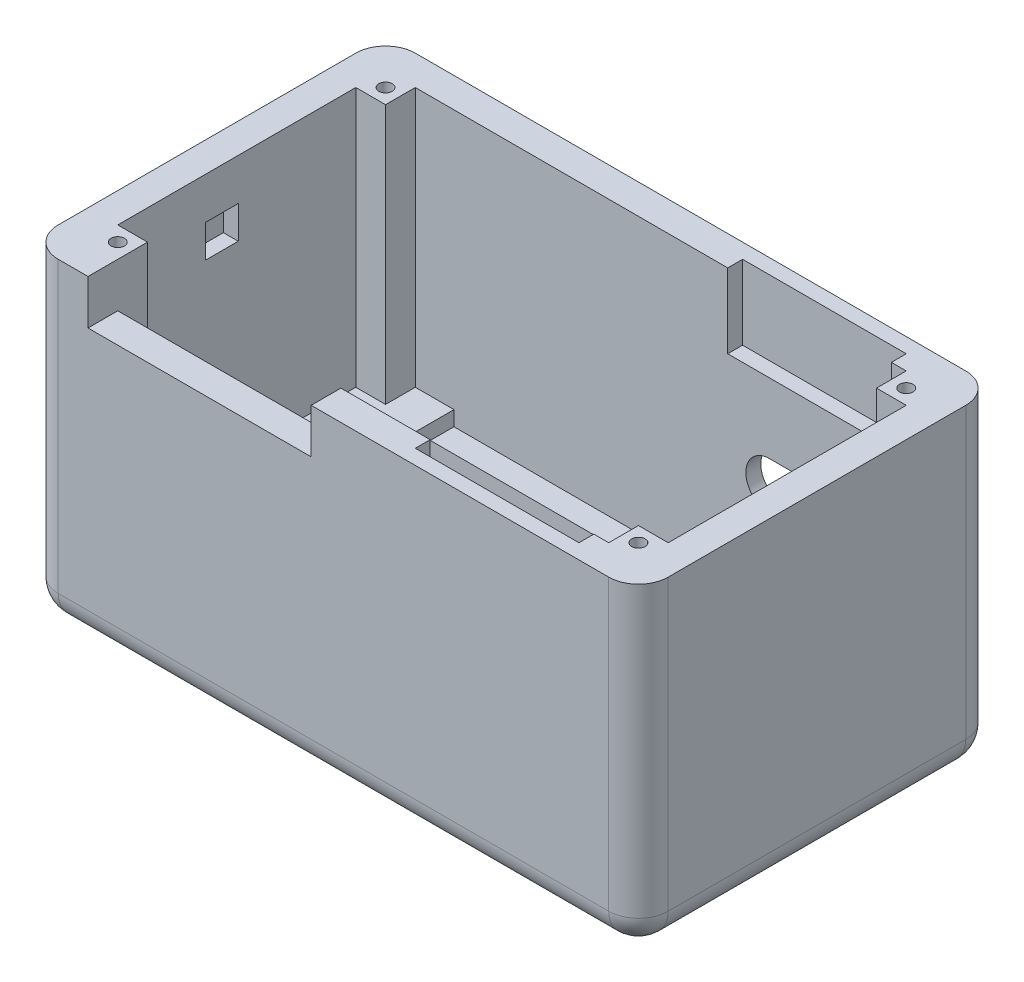
SolidWorks part; units mm, degrees
ref_plane "前视基准面" through (0, 0, 0) normal (0, 0, 1) x (1, 0, 0)
ref_plane "上视基准面" through (0, 0, 0) normal (0, 1, 0) x (1, 0, 0)
ref_plane "右视基准面" through (0, 0, 0) normal (1, 0, 0) x (0, 0, -1)
sketch "草图1" plane through (0, 0, 0) normal (0, 1, 0) x (1, 0, 0)
  line L1 (-72.1576, -30.7504) -> (-31.1576, -30.7504)
  line L2 (-72.1576, -30.7504) -> (-72.1576, -6.7504)
  line L3 (-72.1576, -6.7504) -> (-31.1576, -6.7504)
  line L4 (-31.1576, -30.7504) -> (-31.1576, -6.7504)
  dimension "D1" = 24
  dimension "D2" = 41
extrude "凸台-拉伸1" add sketch "草图1" along normal blind 21.45 contours L2 L1 L4 L3
sketch "草图2" plane through (0, 21.45, 0) normal (0, 1, 0) x (1, 0, 0)
  line L0 (-31.1576, -30.7504) -> (-31.1576, -6.7504) construction
  line L1 (-70.1576, -8.7504) -> (-33.1576, -8.7504)
  line L2 (-70.1576, -8.7504) -> (-70.1576, -28.7504)
  line L3 (-70.1576, -28.7504) -> (-33.1576, -28.7504)
  line L4 (-33.1576, -8.7504) -> (-33.1576, -28.7504)
  line L5 (-72.1576, -30.7504) -> (-31.1576, -30.7504) construction
  line L6 (-72.1576, -30.7504) -> (-72.1576, -6.7504) construction
  line L7 (-72.1576, -6.7504) -> (-31.1576, -6.7504) construction
  dimension "D1" = 2
  dimension "D2" = 2
  dimension "D3" = 2
  dimension "D4" = 2
extrude "切除-拉伸1" cut sketch "草图2" against normal blind 18.45
sketch "草图4" plane through (0, 0, 0) normal (0, -1, 0) x (-1, 0, 0)
  line L0 (72.1576, -30.7504) -> (72.1576, -6.7504) construction
  line L1 (68.9576, -11.5404) -> (53.7476, -11.5404)
  line L2 (68.9576, -11.5404) -> (68.9576, -26.7504)
  line L3 (68.9576, -26.7504) -> (53.7476, -26.7504)
  line L4 (53.7476, -11.5404) -> (53.7476, -26.7504)
  line L6 (72.1576, -30.7504) -> (31.1576, -30.7504) construction
  dimension "D1" = 15.21
  dimension "D2" = 15.21
  dimension "D3" = 3.2
  dimension "D4" = 4
extrude "切除-拉伸2" cut sketch "草图4" against normal blind 15 contours L2 L1 L4 L3
sketch "草图6" plane through (0, 0, 30.7504) normal (0, 0, 1) x (1, 0, 0)
  line L1 (-53.1576, 18.45) -> (-68.1576, 18.45)
  line L2 (-53.1576, 18.45) -> (-53.1576, 21.45)
  line L3 (-53.1576, 21.45) -> (-68.1576, 21.45)
  line L4 (-68.1576, 18.45) -> (-68.1576, 21.45)
  line L5 (-72.1576, 21.45) -> (-72.1576, 0) construction
  line L6 (-72.1576, 21.45) -> (-31.1576, 21.45) construction
  point P9 (-68.1576, 19.95)
  dimension "D2" = 3
  dimension "D3" = 4
  dimension "D4" = 15
extrude "切除-拉伸4" cut sketch "草图6" against normal blind 5
sketch "草图7" plane through (0, 0, 6.7504) normal (0, 0, -1) x (-1, 0, 0)
  line L0 (72.1576, 0) -> (31.1576, 0) construction
  line L3 (44.3376, 10.15) -> (38.1376, 10.15) construction
  line L4 (44.3376, 6.55) -> (38.1376, 6.55)
  line L5 (44.3376, 13.75) -> (38.1376, 13.75)
  line L6 (31.1576, 21.45) -> (31.1576, 0) construction
  arc A2 (44.3376, 6.55) -> (44.3376, 13.75) centre (44.3376, 10.15) ccw
  arc A3 (38.1376, 13.75) -> (38.1376, 6.55) centre (38.1376, 10.15) ccw
  point P2 (34.5376, 10.15)
  point P10 (41.2376, 10.15)
  point P15 (41.2376, 13.75)
  dimension "D1" = 6.55
  dimension "D2" = 3.38
  dimension "D3" = 6.2
  dimension "D4" = 7.2
extrude "切除-拉伸7" cut sketch "草图7" against normal blind 1
sketch "草图9" plane through (0, 0, 7.7504) normal (0, 0, -1) x (-1, 0, 0)
  line L0 (44.3376, 10.15) -> (38.5376, 10.15) construction
  line L1 (44.3376, 8.55) -> (38.5376, 8.55)
  line L2 (44.3376, 11.75) -> (38.5376, 11.75)
  line L3 (44.3376, 13.75) -> (38.1376, 13.75) construction
  arc A0 (44.3376, 8.55) -> (44.3376, 11.75) centre (44.3376, 10.15) ccw
  arc A1 (38.5376, 11.75) -> (38.5376, 8.55) centre (38.5376, 10.15) ccw
  arc A2 (44.3376, 6.55) -> (44.3376, 13.75) centre (44.3376, 10.15) ccw construction
  point P2 (41.4376, 10.15)
  point P12 (47.9376, 10.15)
  point P13 (45.9376, 10.15)
  point P14 (36.9376, 10.15)
  dimension "D1" = 2
  dimension "D2" = 2
  dimension "D3" = 3.2
  dimension "D4" = 9
extrude "切除-拉伸8" cut sketch "草图9" against normal blind 1
sketch "草图11" plane through (0, 3, 0) normal (0, 1, 0) x (1, 0, 0)
  line L0 (-68.9576, -26.7504) -> (-68.9576, -11.5404) construction
  line L1 (-34.6576, -10.3404) -> (-70.1576, -10.3404)
  line L2 (-34.6576, -10.3404) -> (-34.6576, -27.9404)
  line L3 (-34.6576, -27.9404) -> (-70.1576, -27.9404)
  line L4 (-70.1576, -10.3404) -> (-70.1576, -27.9404)
  line L5 (-53.7476, -11.5404) -> (-68.9576, -11.5404) construction
  line L7 (-33.1576, -28.7504) -> (-33.1576, -8.7504) construction
  dimension "D1" = 1.5
  dimension "D2" = 17.6
  dimension "D3" = 1.2
  dimension "D4" = 1.2
extrude "切除-拉伸10" cut sketch "草图11" against normal blind 1.5
sketch "草图13" plane through (0, 21.45, 0) normal (0, 1, 0) x (1, 0, 0)
  line L5 (-33.1576, -28.7504) -> (-33.1576, -8.7504) construction
  line L6 (-53.1576, -28.7504) -> (-33.1576, -28.7504) construction
  line L7 (-47.1576, -28.7504) -> (-36.1576, -28.7504)
  line L8 (-47.1576, -28.7504) -> (-47.1576, -29.7504)
  line L9 (-47.1576, -29.7504) -> (-36.1576, -29.7504)
  line L10 (-36.1576, -28.7504) -> (-36.1576, -29.7504)
  line L11 (-33.1576, -8.7504) -> (-70.1576, -8.7504) construction
  line L12 (-47.1576, -8.7504) -> (-36.1576, -8.7504)
  line L13 (-47.1576, -8.7504) -> (-47.1576, -7.7504)
  line L14 (-47.1576, -7.7504) -> (-36.1576, -7.7504)
  line L15 (-36.1576, -8.7504) -> (-36.1576, -7.7504)
  dimension "D1" = 1
  dimension "D2" = 1
  dimension "D3" = 11
  dimension "D4" = 3
extrude "切除-拉伸12" cut sketch "草图13" against normal blind 5
fillet "圆角2" radius 2 8 edges at (-31.1576, 10.725, 6.7504) (-51.6576, 0, 6.7504) (-51.6576, 0, 30.7504) (-72.1576, 0, 18.7504) (-72.1576, 10.725, 30.7504) (-31.1576, 10.725, 30.7504) (-31.1576, 0, 18.7504) (-72.1576, 10.725, 6.7504)
chamfer "倒角2" distance 1.5 distance2 2 4 edges at (-61.3526, 0, 26.7504) (-53.7476, 0, 19.1454) (-61.3526, 0, 11.5404) (-68.9576, 0, 19.1454) first distance on face at (-61.3526, 0.75, 26.7504) first distance on face at (-53.7476, 0.75, 19.1454) first distance on face at (-61.3526, 0.75, 11.5404) first distance on face at (-68.9576, 0.75, 19.1454)
sketch "草图19" plane through (-70.1576, 0, 0) normal (1, 0, 0) x (0, 0, -1)
  line L0 (-8.7504, 21.45) -> (-28.7504, 21.45) construction
  line L1 (-20.8504, 18.65) -> (-18.6504, 18.65)
  line L2 (-20.8504, 18.65) -> (-20.8504, 16.45)
  line L3 (-20.8504, 16.45) -> (-18.6504, 16.45)
  line L4 (-18.6504, 18.65) -> (-18.6504, 16.45)
  line L5 (-30.7504, 21.45) -> (-30.7504, 18.45) construction
  dimension "D1" = 2.2
  dimension "D2" = 2.2
  dimension "D3" = 2.8
  dimension "D4" = 9.9
extrude "切除-拉伸16" cut sketch "草图19" against normal blind 1
sketch "草图21" plane through (-33.1576, 0, 0) normal (-1, 0, 0) x (0, 0, 1)
  line L0 (28.7504, 3) -> (8.7504, 3) construction
  line L1 (12.5504, 4) -> (8.7504, 4)
  line L2 (12.5504, 4) -> (12.5504, 3)
  line L3 (12.5504, 3) -> (8.7504, 3)
  line L4 (8.7504, 4) -> (8.7504, 3)
  line L6 (28.7504, 3) -> (25.7504, 3)
  line L7 (28.7504, 3) -> (28.7504, 4)
  line L8 (28.7504, 4) -> (25.7504, 4)
  line L9 (25.7504, 3) -> (25.7504, 4)
  dimension "D1" = 3.8
  dimension "D2" = 3
  dimension "D3" = 1
extrude "凸台-拉伸4" add sketch "草图21" along normal blind 3
fillet "圆角8" radius 1 1 edges at (-34.6576, 3, 19.1504) type face fillet first side face at (-34.6576, 2.5, 19.1438) second side face at (-33.9076, 3, 19.1504)
sketch "草图24" plane through (-33.1576, 0, 0) normal (-1, 0, 0) x (0, 0, 1)
  line L0 (25.7504, 3) -> (12.5504, 3) construction
  line L1 (25.7504, 3) -> (12.5504, 3)
  line L2 (25.7504, 3) -> (25.7504, 12.5)
  line L3 (25.7504, 12.5) -> (12.5504, 12.5)
  line L4 (12.5504, 3) -> (12.5504, 12.5)
  line L5 (25.7504, 4) -> (25.7504, 3) construction
  line L6 (12.5504, 3) -> (12.5504, 4) construction
  dimension "D1" = 9.5
extrude "切除-拉伸17" cut sketch "草图24" against normal blind 1
sketch "草图27" plane through (0, 0, 8.7504) normal (0, 0, 1) x (1, 0, 0)
  line L1 (-70.1576, 3) -> (-65.5576, 3)
  line L2 (-70.1576, 3) -> (-70.1576, 4)
  line L3 (-70.1576, 4) -> (-65.5576, 4)
  line L4 (-65.5576, 3) -> (-65.5576, 4)
  dimension "D1" = 1
  dimension "D2" = 4.6
extrude "凸台-拉伸6" add sketch "草图27" along normal up to next
sketch "草图28" plane through (0, 4, 0) normal (0, 1, 0) x (1, 0, 0)
  line L1 (-70.1576, -8.7504) -> (-68.1576, -8.7504)
  line L2 (-70.1576, -8.7504) -> (-70.1576, -10.7504)
  line L3 (-70.1576, -10.7504) -> (-68.1576, -10.7504)
  line L4 (-68.1576, -8.7504) -> (-68.1576, -10.7504)
  line L5 (-33.1576, -8.7504) -> (-35.1576, -8.7504)
  line L6 (-33.1576, -8.7504) -> (-33.1576, -10.7504)
  line L7 (-33.1576, -10.7504) -> (-35.1576, -10.7504)
  line L8 (-35.1576, -8.7504) -> (-35.1576, -10.7504)
  line L9 (-70.1576, -28.7504) -> (-68.1576, -28.7504)
  line L10 (-70.1576, -28.7504) -> (-70.1576, -26.7504)
  line L11 (-70.1576, -26.7504) -> (-68.1576, -26.7504)
  line L12 (-68.1576, -28.7504) -> (-68.1576, -26.7504)
  line L13 (-33.1576, -28.7504) -> (-35.1576, -28.7504)
  line L14 (-33.1576, -28.7504) -> (-33.1576, -26.7504)
  line L15 (-33.1576, -26.7504) -> (-35.1576, -26.7504)
  line L16 (-35.1576, -28.7504) -> (-35.1576, -26.7504)
  dimension "D1" = 2
extrude "凸台-拉伸7" add sketch "草图28" along normal up to surface (17.45 mm away) up to face at (-49.8242, 21.45, 20.5838)
sketch "草图29" plane through (0, 21.45, 0) normal (0, 1, 0) x (1, 0, 0)
  line L1 (-68.1576, -30.7504) -> (-68.1576, -26.7504) construction
  line L2 (-70.1576, -10.7504) -> (-68.1576, -10.7504) construction
  line L3 (-35.1576, -8.7504) -> (-35.1576, -10.7504) construction
  line L5 (-70.1576, -30.7504) -> (-68.1576, -30.7504) construction
  circle A0 centre (-69.1576, -9.7504) radius 0.45
  circle A1 centre (-69.1576, -27.7504) radius 0.45
  circle A2 centre (-34.1576, -9.7504) radius 0.45
  circle A3 centre (-34.1576, -27.7504) radius 0.45
  dimension "D1" = 0.9
  dimension "D2" = 3
  dimension "D3" = 1
  dimension "D4" = 1
  dimension "D5" = 1
extrude "切除-拉伸18" cut sketch "草图29" against normal blind 6
